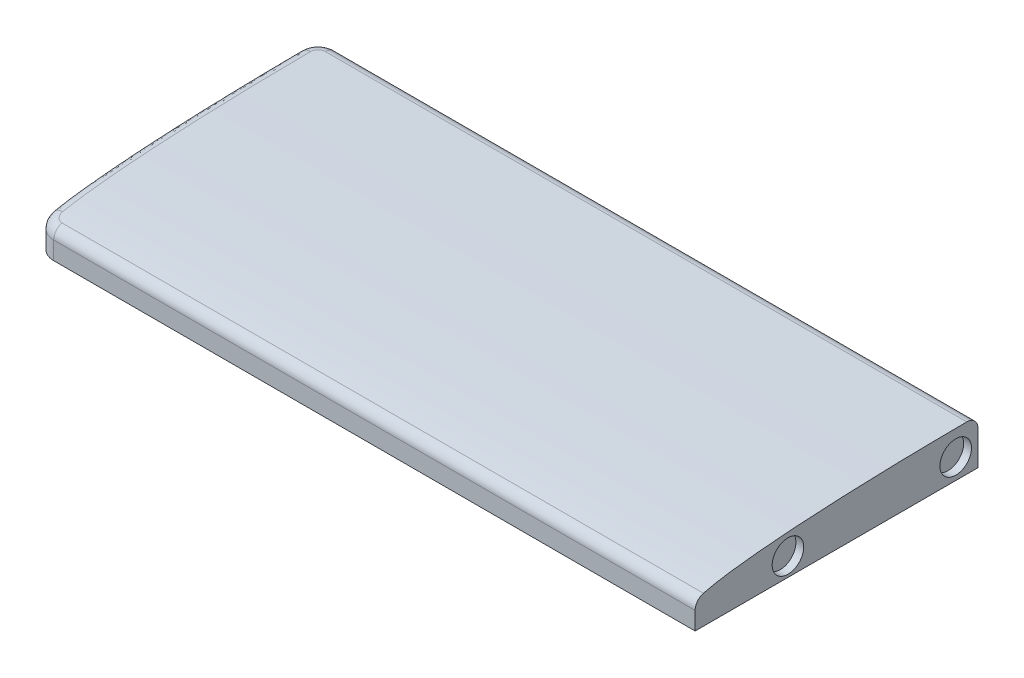
SolidWorks part; units mm, degrees
ref_plane "Front Plane" through (0, 0, 0) normal (0, 0, 1) x (1, 0, 0)
ref_plane "Top Plane" through (0, 0, 0) normal (0, 1, 0) x (1, 0, 0)
ref_plane "Right Plane" through (0, 0, 0) normal (1, 0, 0) x (0, 0, -1)
sketch "Sketch1" plane through (0, 0, 0) normal (0, 1, 0) x (1, 0, 0)
  line L0 (-177.8, -38.1) -> (-177.8, 38.1)
  line L1 (-177.8, -38.1) -> (177.8, -38.1)
  line L2 (-177.8, 38.1) -> (177.8, 38.1)
  line L3 (177.8, -38.1) -> (177.8, 38.1)
  line L4 (-177.8, -38.1) -> (177.8, 38.1) construction
  line L5 (-177.8, 38.1) -> (177.8, -38.1) construction
  point P1 (0, 0)
  dimension "D1" = 355.6
  dimension "D2" = 76.2
extrude "Boss-Extrude1" add sketch "Sketch1" along normal blind 12.7
fillet "Fillet3" radius 5 4 edges at (-177.8, 6.35, -38.1) (-177.8, 6.35, 38.1) (177.8, 6.35, -38.1) (177.8, 6.35, 38.1)
sketch "Sketch2" plane through (0, 0, 0) normal (1, 0, 0) x (0, 0, -1)
  line L1 (-39.2698, 6.4191) -> (-45.4035, 6.4191)
  line L2 (-45.4035, 6.4191) -> (-41.7619, 18.8492)
  line L3 (-41.7619, 18.8492) -> (38.1, 18.8492)
  line L4 (38.1, 18.8492) -> (38.1, 12.7)
  line L5 (38.1, 12.7) -> (38.1, 0) construction
  ellipse E0 centre (38.1, 6.35) end of major axis (-39.2744, 6.35) minor radius 6.35 (38.1, 12.7) -> (-39.2698, 6.4191) ccw
extrude "Cut-Extrude1" cut sketch "Sketch2" against normal through all both and the other way through all
fillet "Fillet7" radius 3 8 edges at (0, 12.7, -38.1) (176.7044, 12.6981, -36.2234) (177.8, 11.5305, 6.6448) (175.6948, 7.8186, 37.1768) (0, 7.4522, 38.1) (-176.6632, 8.1011, 36.2742) (-177.8, 11.5305, 6.6448) (-175.9235, 12.6994, -37.0044)
split "Split1" trim tools "Right Plane" bodies to split 102 resulting bodies 104
sketch "Sketch6" plane through (0, 0, 0) normal (1, 0, 0) x (0, 0, -1)
  line L0 (38.1, 0) -> (38.1, 9.6952) construction
  line L2 (-38.1, 0) -> (38.1, 0) construction
  line L3 (-38.1, 5.3134) -> (-38.1, 0) construction
  circle A0 centre (32.1, 6) radius 4.25
  circle A1 centre (-13.1, 5.5) radius 4.25
  dimension "D1" = 8.5
  dimension "D2" = 25
  dimension "D3" = 6
  dimension "D4" = 6
  dimension "D5" = 5.5
extrude "Cut-Extrude2" cut sketch "Sketch6" against normal blind 2.1
sketch "Sketch7" plane through (0, 0, 0) normal (0, -1, 0) x (1, 0, 0)
  line L0 (-177.8, -33.1) -> (-177.8, 33.1) construction
  line L1 (-172.8, 38.1) -> (0, 38.1) construction
  line L2 (0, -38.1) -> (-172.8, -38.1) construction
  circle A0 centre (-168.8, 29.1) radius 4.5
  circle A1 centre (-9, 29.1) radius 4.5
  circle A2 centre (-9, -29.1) radius 4.5
  circle A3 centre (-168.8, -29.1) radius 4.5
  point P12 (0, 0)
  point P13 (0, 0)
  point P14 (0, 0)
  point P15 (0, 0)
  point P18 (0, 0)
  dimension "D1" = 9
  dimension "D2" = 9
  dimension "D3" = 9
  dimension "D4" = 9
  dimension "D5" = 9
extrude "Cut-Extrude3" cut sketch "Sketch7" against normal blind 0.125
chamfer "Chamfer1" distance 0.5 angle 45 10 edges at (-86.4, 0, -38.1) (-176.3355, 0, -36.6355) (-177.8, 0, 0) (-176.3355, 0, 36.6355) (-86.4, 0, 38.1) (0, 0, 0) (-168.8, 0, 24.6) (-9, 0, 24.6) (-9, 0, -33.6) (-168.8, 0, -33.6)
